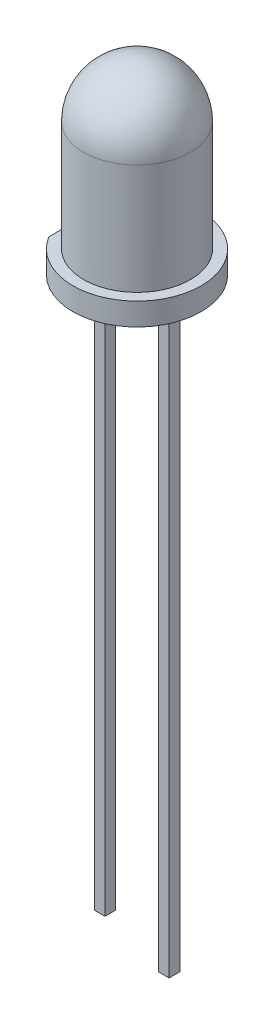
SolidWorks part; units mm, degrees
ref_plane "Front Plane" through (0, 0, 0) normal (0, 0, 1) x (1, 0, 0)
ref_plane "Top Plane" through (0, 0, 0) normal (0, 1, 0) x (1, 0, 0)
ref_plane "Right Plane" through (0, 0, 0) normal (1, 0, 0) x (0, 0, -1)
sketch "Sketch1" plane through (0, 0, 0) normal (0, 0, 1) x (1, 0, 0)
  line L0 (0, 0) -> (3, 0)
  line L1 (3, 0) -> (3, 1.05)
  line L2 (3, 1.05) -> (2.5, 1.05)
  line L3 (2.5, 1.05) -> (2.5, 6.21)
  line L4 (0, 8.71) -> (0, 6.21)
  line L5 (0, 6.21) -> (0, 0)
  arc A0 (2.5, 6.21) -> (0, 8.71) centre (0, 6.21) ccw
  dimension "D1" = 2.5
  dimension "D2" = 1.05
  dimension "D3" = 3
  dimension "D4" = 8.71
revolve "Revolve1" add sketch "Sketch1" angle 360 about L5
sketch "Sketch2" plane through (0, 0, 0) normal (0, -1, 0) x (1, 0, 0)
  line L0 (3, 0) -> (-2.55, 0) construction
  line L1 (-5.5707, 2.6875) -> (-2.55, 2.6875)
  line L2 (-5.5707, 2.6875) -> (-5.5707, -4.8308)
  line L3 (-5.5707, -4.8308) -> (-2.55, -4.8308)
  line L4 (-2.55, 2.6875) -> (-2.55, -4.8308)
  circle A0 centre (0, 0) radius 3 construction
  dimension "D1" = 5.55
extrude "Cut-Extrude1" cut sketch "Sketch2" against normal blind 10
sketch "Sketch3" plane through (0, 0, 0) normal (0, -1, 0) x (1, 0, 0)
  line L0 (0, 0) -> (0, 1.1247) construction
  line L1 (-1.75, 0.25) -> (-1.25, 0.25)
  line L2 (-1.75, 0.25) -> (-1.75, -0.25)
  line L3 (-1.75, -0.25) -> (-1.25, -0.25)
  line L4 (-1.25, 0.25) -> (-1.25, -0.25)
  line L5 (1.25, 0.25) -> (1.25, -0.25)
  line L6 (1.75, -0.25) -> (1.25, -0.25)
  line L7 (1.75, 0.25) -> (1.75, -0.25)
  line L8 (1.75, 0.25) -> (1.25, 0.25)
  point P7 (-1.25, 0)
  dimension "D1" = 0.5
  dimension "D2" = 0.5
  dimension "D3" = 1.25
extrude "Boss-Extrude1" add sketch "Sketch3" along normal blind 27.5
sketch "Sketch4" plane through (0, 0, 0) normal (0, 0, 1) x (1, 0, 0)
  line L0 (1.75, -27.5) -> (1.25, -27.5) construction
  line L1 (-5.2677, -26.5) -> (0, -26.5)
  line L2 (-5.2677, -26.5) -> (-5.2677, -29.6259)
  line L3 (-5.2677, -29.6259) -> (0, -29.6259)
  line L4 (0, -26.5) -> (0, -29.6259)
  dimension "D1" = 1
extrude "Cut-Extrude2" cut sketch "Sketch4" against normal mid plane 27.5
ref_axis "beam axis" through (0, 10.5205, 0) along (0, -1, 0)
sketch "Sketch5" plane through (0, 0, 0) normal (0, 0, 1) x (1, 0, 0)
  line L0 (0.2588, 4.4659) -> (637.235, 2381.6935)
  line L1 (0, 10.5205) -> (0, -29.3105) construction
  line L2 (637.235, 2381.6935) -> (0, 2381.6935) construction
  line L3 (0.2588, 4.4659) -> (0, 3.5) construction
  line L5 (637.235, 2381.6935) -> (637.3316, 2381.6676)
  line L6 (637.3316, 2381.6676) -> (0.3554, 4.44)
  line L7 (0.3554, 4.44) -> (0.2588, 4.4659)
  line L8 (-2.55, 0) -> (3, 0) construction
  line L9 (0, 0) -> (0, 2381.6935) construction
  dimension "D1" = 1
  dimension "D2" = 3.5
  dimension "D3" = 15
  dimension "D4" = 0.1
revolve "beam cone 1m long" [suppressed] add sketch "Sketch5" angle 360 about L9
